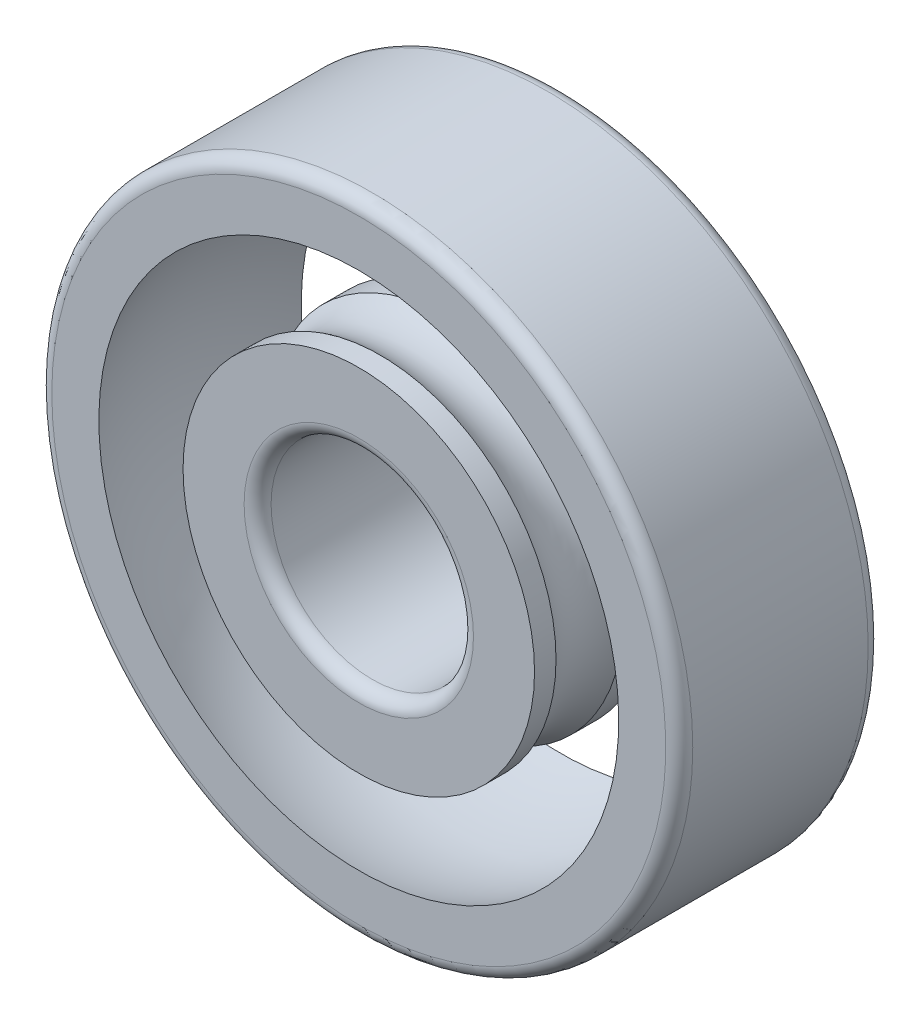
SolidWorks part; units mm, degrees
material "Легированная сталь"
ref_plane "Спереди" through (0, 0, 0) normal (0, 0, 1) x (1, 0, 0)
ref_plane "Сверху" through (0, 0, 0) normal (0, 1, 0) x (1, 0, 0)
ref_plane "Справа" through (0, 0, 0) normal (1, 0, 0) x (0, 0, -1)
sketch "Эскиз1" plane through (0, 0, 0) normal (1, 0, 0) x (0, 0, -1)
  line L0 (0, 5.21) -> (0.6368, 5.21)
  line L1 (0, 9.5) -> (6, 9.5)
  line L2 (0, 9.5) -> (0, 7.7054)
  line L3 (0, 3) -> (6, 3)
  line L4 (6, 9.5) -> (6, 7.7054)
  line L5 (6, 5.21) -> (5.3632, 5.21)
  line L6 (3, 3) -> (3, -49997) construction
  line L7 (0, 0) -> (50000, 0) construction
  line L8 (0, 5.21) -> (0, 3)
  line L9 (6, 5.21) -> (6, 3)
  line L10 (2.6132, 5.21) -> (3.3868, 5.21)
  arc A0 (3.3868, 5.21) -> (5.3632, 5.21) centre (4.375, 6.5) ccw
  arc A1 (0.6368, 5.21) -> (2.6132, 5.21) centre (1.625, 6.5) ccw
  arc A3 (6, 7.7054) -> (0, 7.7054) centre (3, 0) ccw
  point P15 (3, 3)
  point P18 (3, 0)
  dimension "D4" = 3.25
  dimension "D5" = 6.5
  dimension "D6" = 8.2688
  dimension "D1" = 9.5
  dimension "D2" = 3
  dimension "D3" = 6
  dimension "D7" = 2.21
revolve "Повернуть1" add sketch "Эскиз1" angle 360 about L7
fillet "Скругление1" radius 0.4 2 edges at (3, 0, 0) (3, 0, -6)
fillet "Скругление2" radius 0.4 2 edges at (9.5, 0, -6) (9.5, 0, 0)
